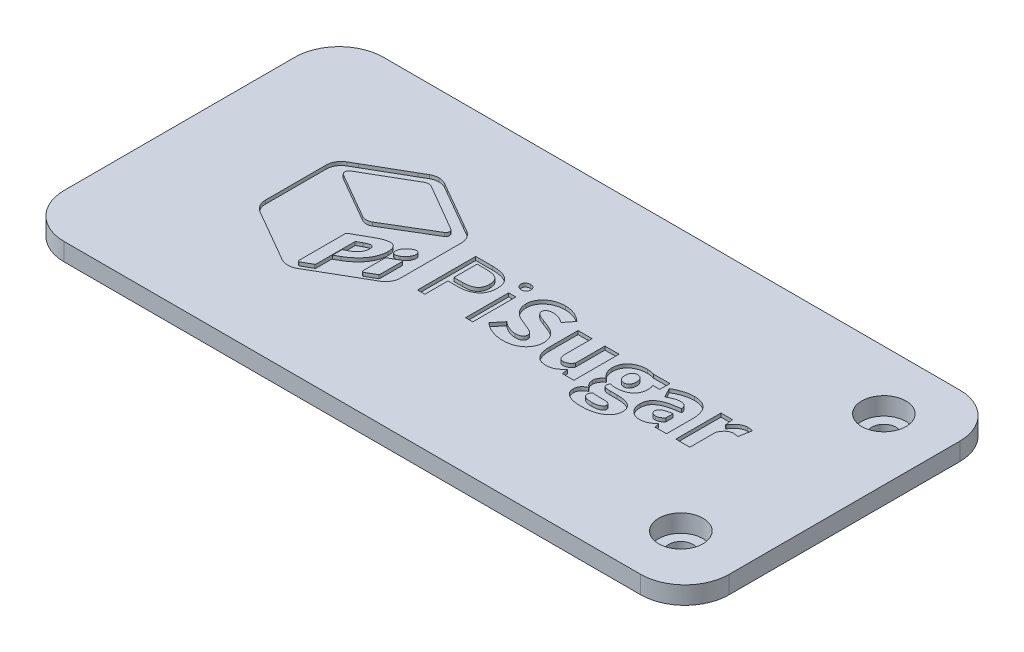
SolidWorks part; units mm, degrees
ref_plane "前视基准面" through (0, 0, 0) normal (0, 0, 1) x (1, 0, 0)
ref_plane "上视基准面" through (0, 0, 0) normal (0, 1, 0) x (1, 0, 0)
ref_plane "右视基准面" through (0, 0, 0) normal (1, 0, 0) x (0, 0, -1)
sketch "zero" plane through (0, 0, 0) normal (0, 1, 0) x (1, 0, 0)
  line L1 (-29.5, 15) -> (29.5, 15)
  line L2 (-32.5, 12) -> (-32.5, -12)
  line L3 (-29.5, -15) -> (29.5, -15)
  line L4 (32.5, 12) -> (32.5, -12)
  line L5 (-32.5, 15) -> (32.5, -15) construction
  line L6 (-32.5, -15) -> (32.5, 15) construction
  line L7 (-25.7, -15) -> (-14.5, -15)
  line L8 (-25.7, -15) -> (-25.7, -9.6569)
  line L9 (-25.7, -9.6569) -> (-14.5, -9.6569)
  line L10 (-14.5, -15) -> (-14.5, -9.6569)
  line L11 (5.2, -15) -> (12.7, -15)
  line L12 (5.2, -15) -> (5.2, -11)
  line L13 (5.2, -11) -> (12.7, -11)
  line L14 (12.7, -15) -> (12.7, -11)
  line L15 (17.8, -15) -> (25.3, -15)
  line L16 (17.8, -15) -> (17.8, -11)
  line L17 (17.8, -11) -> (25.3, -11)
  line L18 (25.3, -15) -> (25.3, -11)
  line L19 (-32.5, 7.7) -> (-19.5, 7.7)
  line L20 (-32.5, 7.7) -> (-32.5, -4.3)
  line L21 (-32.5, -4.3) -> (-19.5, -4.3)
  line L22 (-19.5, 7.7) -> (-19.5, -4.3)
  line L23 (-25.5, 14) -> (25.5, 14)
  line L24 (-25.5, 14) -> (-25.5, 8.8)
  line L25 (-25.5, 8.8) -> (25.5, 8.8)
  line L26 (25.5, 14) -> (25.5, 8.8)
  line L27 (-19.5, 7.2329) -> (-35.5, 7.2329)
  line L28 (-19.5, 7.2329) -> (-19.5, -3.7671)
  line L29 (-19.5, -3.7671) -> (-35.5, -3.7671)
  line L30 (-35.5, 7.2329) -> (-35.5, -3.7671)
  arc A0 (29.5, -15) -> (32.5, -12) centre (29.5, -12) ccw
  arc A1 (29.5, 15) -> (32.5, 12) centre (29.5, 12) cw
  arc A2 (-32.5, -12) -> (-29.5, -15) centre (-29.5, -12) ccw
  arc A3 (-29.5, 15) -> (-32.5, 12) centre (-29.5, 12) ccw
  circle A4 centre (-29, 11.4) radius 3
  circle A5 centre (-29, -11.5) radius 3
  circle A6 centre (29, 11.4) radius 3
  circle A7 centre (29, -11.5) radius 3
  circle A8 centre (-29, 11.4) radius 1.375
  circle A9 centre (-29, -11.5) radius 1.375
  circle A10 centre (29, -11.5) radius 1.375
  circle A11 centre (29, 11.4) radius 1.375
  point P0 (0, 0)
  dimension "D3" = 3
  dimension "D4" = 6
  dimension "D9" = 2.75
  dimension "D1" = 65
  dimension "D2" = 30
  dimension "D5" = 3.6
  dimension "D6" = 3.5
  dimension "D7" = 3.5
  dimension "D8" = 3.5
  dimension "D10" = 12
  dimension "D11" = 7.3
  dimension "D12" = 13
  dimension "D13" = 11.2
  dimension "D14" = 6.8
  dimension "D15" = 19.7
  dimension "D16" = 7.5
  dimension "D17" = 7.5
  dimension "D18" = 5.1
  dimension "D19" = 4
  dimension "D20" = 5.2
  dimension "D21" = 7
  dimension "D22" = 7
  dimension "D23" = 1
  dimension "D24" = 11
  dimension "D25" = 16
sketch "sugar" plane through (0, 0, 0) normal (0, 1, 0) x (1, 0, 0)
  line L1 (-29.5, 15) -> (29.5, 15)
  line L2 (-32.5, 12) -> (-32.5, -12)
  line L3 (-29.5, -15) -> (29.5, -15)
  line L4 (32.5, 12) -> (32.5, -12)
  line L5 (-32.5, 15) -> (32.5, -15) construction
  line L6 (-32.5, -15) -> (32.5, 15) construction
  line L7 (23.5, -11.5) -> (19.5, -11.5)
  line L8 (23.5, -11.5) -> (23.5, -13.9082)
  line L9 (23.5, -13.9082) -> (19.5, -13.9082)
  line L10 (19.5, -11.5) -> (19.5, -13.9082)
  line L11 (16, -11.0071) -> (8.5, -11.0071)
  line L12 (16, -11.0071) -> (16, -15)
  line L13 (16, -15) -> (8.5, -15)
  line L14 (8.5, -11.0071) -> (8.5, -15)
  line L15 (20.5, -13.9082) -> (22.5, -13.9082)
  line L16 (20.5, -13.9082) -> (20.5, -14.8173)
  line L17 (20.5, -14.8173) -> (22.5, -14.8173)
  line L18 (22.5, -13.9082) -> (22.5, -14.8173)
  arc A0 (29.5, 15) -> (32.5, 12) centre (29.5, 12) cw
  arc A1 (29.5, -15) -> (32.5, -12) centre (29.5, -12) ccw
  arc A2 (-32.5, -12) -> (-29.5, -15) centre (-29.5, -12) ccw
  arc A3 (-29.5, 15) -> (-32.5, 12) centre (-29.5, 12) ccw
  circle A4 centre (-29, 11.4) radius 3
  circle A5 centre (-29, 11.4) radius 1.375
  circle A6 centre (-29, -11.5) radius 3
  circle A7 centre (-29, -11.5) radius 1.375
  circle A8 centre (29, 11.4) radius 3
  circle A9 centre (29, 11.4) radius 1.375
  circle A10 centre (29, -11.5) radius 3
  circle A11 centre (29, -11.5) radius 1.375
  dimension "D3" = 3
  dimension "D1" = 65
  dimension "D2" = 30
  dimension "D4" = 9
  dimension "D5" = 4
  dimension "D6" = 3.5
  dimension "D7" = 7.5
  dimension "D8" = 2
  dimension "D9" = 1
sketch "case" plane through (0, 0, 0) normal (0, 1, 0) x (1, 0, 0)
  line L1 (-34.0422, 18) -> (30.9578, 18)
  line L2 (-39.0422, 13) -> (-39.0422, -13)
  line L3 (-34.0422, -18) -> (30.9578, -18)
  line L4 (35.9578, 13) -> (35.9578, -13)
  line L5 (-39.0422, 18) -> (35.9578, -18) construction
  line L6 (-39.0422, -18) -> (35.9578, 18) construction
  arc A0 (-39.0422, -13) -> (-34.0422, -18) centre (-34.0422, -13) ccw
  arc A1 (30.9578, -18) -> (35.9578, -13) centre (30.9578, -13) ccw
  arc A2 (30.9578, 18) -> (35.9578, 13) centre (30.9578, 13) cw
  arc A3 (-34.0422, 18) -> (-39.0422, 13) centre (-34.0422, 13) ccw
  point P0 (-1.5422, 0)
  point P3 (-1.5422, 0)
  dimension "D3" = 5
  dimension "D1" = 75
  dimension "D2" = 36
extrude "凸台-拉伸2" add sketch "case" along normal blind 2
sketch "草图2" plane through (0, 0, 0) normal (0, 1, 0) x (1, 0, 0)
  line L4 (-34.0422, -14.7) -> (30.9578, -14.7)
  line L5 (32.6578, -13) -> (32.6578, 13)
  line L6 (30.9578, 14.7) -> (-34.0422, 14.7)
  line L7 (-35.7422, 13) -> (-35.7422, -13)
  line L12 (33.8578, -13) -> (33.8578, 13)
  line L13 (30.9578, 15.9) -> (-34.0422, 15.9)
  line L14 (-36.9422, 13) -> (-36.9422, -13)
  line L15 (-34.0422, -15.9) -> (30.9578, -15.9)
  arc A4 (30.9578, -14.7) -> (32.6578, -13) centre (30.339, -12.3812) ccw
  arc A5 (32.6578, 13) -> (30.9578, 14.7) centre (30.339, 12.3812) ccw
  arc A6 (-34.0422, 14.7) -> (-35.7422, 13) centre (-33.4234, 12.3812) ccw
  arc A7 (-35.7422, -13) -> (-34.0422, -14.7) centre (-33.4234, -12.3812) ccw
  arc A12 (30.9578, -15.9) -> (33.8578, -13) centre (30.5796, -12.6217) ccw
  arc A13 (33.8578, 13) -> (30.9578, 15.9) centre (30.5796, 12.6217) ccw
  arc A14 (-34.0422, 15.9) -> (-36.9422, 13) centre (-33.6639, 12.6217) ccw
  arc A15 (-36.9422, -13) -> (-34.0422, -15.9) centre (-33.6639, -12.6217) ccw
  point P13 (0, 0)
extrude "凸台-拉伸3" add sketch "草图2" against normal blind 1
sketch "草图4" plane through (0, 0, 0) normal (0, 1, 0) x (1, 0, 0)
  line L1 (-35.7422, -5) -> (-31.7422, -5)
  line L2 (-35.7422, -5) -> (-35.7422, 5)
  line L3 (-35.7422, 5) -> (-31.7422, 5)
  line L4 (-31.7422, -5) -> (-31.7422, 5)
  line L5 (-35.7422, -5) -> (-31.7422, 5) construction
  line L6 (-35.7422, 5) -> (-31.7422, -5) construction
  line L7 (-35.7422, 13) -> (-35.7422, -13) construction
  point P0 (-33.7422, 0)
  dimension "D1" = 4
  dimension "D2" = 10
  dimension "D3" = 0
ref_plane "基准面1" through (33.8578, 0, 0) normal (1, 0, 0) x (0, 0, -1)
extrude "凸台-拉伸7" add sketch "草图4" against normal blind 2.2
ref_plane "基准面2" through (-36.9422, 0, 0) normal (-1, 0, 0) x (0, 0, 1)
ref_plane "基准面3" through (0, 2, 0) normal (0, 1, 0) x (1, 0, 0)
sketch "草图7" plane through (0, 2, 0) normal (0, 1, 0) x (1, 0, 0)
  line L0 (30.9578, 18) -> (-34.0422, 18) construction
  line L1 (-34.0422, -18) -> (30.9578, -18) construction
  line L2 (35.9578, -13) -> (35.9578, 13) construction
  circle A0 centre (28.9978, 11.4) radius 1.375
  circle A1 centre (28.9978, -11.5) radius 1.375
  dimension "D1" = 2.75
  dimension "D2" = 6.6
  dimension "D3" = 6.5
  dimension "D4" = 6.96
sketch "草图9" plane through (0, 2, 0) normal (0, 1, 0) x (1, 0, 0)
  circle A0 centre (28.9978, 11.4) radius 2.5
  circle A1 centre (28.9978, -11.5) radius 2.5
  dimension "D1" = 5
sketch "草图10" plane through (0, 2, 0) normal (0, 1, 0) x (1, 0, 0)
  circle A0 centre (28.9978, 11.4) radius 3.5
  circle A1 centre (28.9978, -11.5) radius 3.5
  dimension "D1" = 7
extrude "凸台-拉伸10" add sketch "草图10" against normal blind 3
extrude "切除-拉伸3" cut sketch "草图9" against normal blind 2
extrude "切除-拉伸4" cut sketch "草图7" against normal blind 4
ref_plane "基准面4" through (-31.7422, 0, 0) normal (1, 0, 0) x (0, 0, -1)
sketch "草图12" plane through (-31.7422, 0, 0) normal (1, 0, 0) x (0, 0, -1)
  line L1 (-5, -2.2) -> (5, -2.2)
  line L2 (-5, -2.2) -> (-5, -1)
  line L3 (-5, -1) -> (5, -1)
  line L4 (5, -2.2) -> (5, -1)
extrude "凸台-拉伸11" add sketch "草图12" against normal blind 6.7
chamfer "倒角5" distance 1 angle 45 1 edges at (-38.4422, -1, 0)
chamfer "倒角6" distance 1 angle 45 3 edges at (-33.7422, 0, -5) (-31.7422, 0, 0) (-33.7422, 0, 5)
chamfer "倒角8" distance 1 angle 45 1 edges at (-31.7422, -2.2, 0)
sketch "草图14" plane through (0, 2, 0) normal (0, 1, 0) x (1, 0, 0)
  line L0 (-12.3681, 5.7189) -> (-13.1887, 6.1919)
  line L1 (-13.1887, 6.1919) -> (-17.4456, 8.648)
  line L2 (-17.4456, 8.648) -> (-18.2661, 9.1267)
  line L3 (-19.9872, 9.1267) -> (-20.8078, 8.648)
  line L4 (-20.8078, 8.648) -> (-25.0647, 6.1919)
  line L5 (-25.0647, 6.1919) -> (-25.8853, 5.7189)
  line L6 (-26.7458, 4.2316) -> (-26.7458, -2.584)
  line L7 (-25.8853, -4.0714) -> (-25.0647, -4.5444)
  line L8 (-25.0647, -4.5444) -> (-20.8078, -7.0005)
  line L9 (-20.8078, -7.0005) -> (-19.9872, -7.4792)
  line L10 (-18.2661, -7.4792) -> (-17.4456, -7.0005)
  line L11 (-17.4456, -7.0005) -> (-13.1887, -4.5444)
  line L12 (-13.1887, -4.5444) -> (-12.3681, -4.0714)
  line L13 (-11.5076, -2.584) -> (-11.5076, 4.2316)
  line L14 (-24.7911, 5.0408) -> (-19.5256, 8.0839)
  line L15 (-18.7221, 8.0839) -> (-13.485, 5.0351)
  line L16 (-13.4793, 4.3341) -> (-18.5682, 1.2911)
  line L17 (-16.9897, -3.8662) -> (-17.5823, -4.1967)
  line L18 (-17.6394, -4.2936) -> (-17.6394, -6.0032)
  line L19 (-17.6963, -6.1001) -> (-18.8019, -6.7269)
  line L20 (-18.9671, -6.6301) -> (-18.9671, -1.3531)
  line L21 (-18.9102, -1.2562) -> (-17.0296, -0.1906)
  line L22 (-13.0862, -3.5129) -> (-14.1803, -4.134)
  line L23 (-14.3455, -4.0372) -> (-14.3455, -1.5241)
  line L24 (-14.2885, -1.4272) -> (-13.1944, -0.8117)
  line L25 (-13.0291, -0.9086) -> (-13.0291, -3.416)
  line L26 (-17.0581, -2.8519) -> (-17.5823, -3.114)
  line L27 (-17.6394, -2.9943) -> (-17.6394, -1.6494)
  line L28 (-17.5823, -1.5526) -> (-17.0923, -1.279)
  line L29 (-7.5129, 3.7529) -> (-9.3877, 3.7529)
  line L30 (-9.3877, 3.7529) -> (-9.3877, -2.812)
  line L31 (-9.3877, -2.812) -> (-8.5557, -2.812)
  line L32 (-8.5557, -2.812) -> (-8.5557, -0.2077)
  line L33 (-8.5557, -0.2077) -> (-7.4672, -0.2077)
  line L34 (-7.5755, 0.4648) -> (-8.5557, 0.4648)
  line L35 (-8.5557, 0.4648) -> (-8.5557, 3.0804)
  line L36 (-8.5557, 3.0804) -> (-7.6097, 3.0804)
  line L37 (-3.974, 2.0547) -> (-3.974, -2.812)
  line L38 (-3.974, -2.812) -> (-3.159, -2.812)
  line L39 (-3.159, -2.812) -> (-3.159, 2.0547)
  line L40 (-3.159, 2.0547) -> (-3.974, 2.0547)
  line L41 (1.548, 0.9776) -> (0.716, 1.3082)
  line L42 (1.8728, 2.0946) -> (2.6707, 3.0975)
  line L43 (-0.5605, 0.1342) -> (0.2886, -0.2248)
  line L44 (-1.2614, -0.8744) -> (-2.1674, -1.98)
  line L45 (6.6541, 2.2826) -> (6.6541, -1.0568)
  line L46 (5.2123, -0.6693) -> (5.2123, 2.2826)
  line L47 (5.2123, 2.2826) -> (3.6223, 2.2826)
  line L48 (3.6223, 2.2826) -> (3.6223, -0.8687)
  line L49 (6.8022, -2.111) -> (6.8364, -2.111)
  line L50 (6.8364, -2.111) -> (6.9504, -2.812)
  line L51 (6.9504, -2.812) -> (8.2496, -2.812)
  line L52 (8.2496, -2.812) -> (8.2496, 2.2826)
  line L53 (8.2496, 2.2826) -> (6.6541, 2.2826)
  line L54 (12.1019, -1.809) -> (11.2984, -1.809)
  line L55 (13.1961, 1.1315) -> (13.9825, 1.1315)
  line L56 (13.9825, 1.1315) -> (13.9825, 2.2826)
  line L57 (13.9825, 2.2826) -> (12.1134, 2.2826)
  line L58 (9.8623, -0.7605) -> (9.8623, -0.7946)
  line L59 (9.7655, -2.6239) -> (9.7655, -2.6695)
  line L60 (11.3155, -3.0285) -> (11.8, -3.0285)
  line L61 (14.4384, 1.7413) -> (14.9968, 0.6927)
  line L62 (17.2421, -2.2991) -> (17.282, -2.2991)
  line L63 (17.282, -2.2991) -> (17.3959, -2.812)
  line L64 (17.3959, -2.812) -> (18.6953, -2.812)
  line L65 (18.6953, -2.812) -> (18.6953, 0.0829)
  line L66 (17.0997, -0.4812) -> (17.0997, -1.2961)
  line L67 (21.1856, 1.3994) -> (21.1514, 1.3994)
  line L68 (21.1514, 1.3994) -> (21.0432, 2.2826)
  line L69 (21.0432, 2.2826) -> (19.7439, 2.2826)
  line L70 (19.7439, 2.2826) -> (19.7439, -2.812)
  line L71 (19.7439, -2.812) -> (21.3281, -2.812)
  line L72 (21.3281, -2.812) -> (21.3281, 0.1)
  line L73 (22.9864, 0.9321) -> (23.2542, 2.3054)
  line L74 (-17.5823, -3.114) -> (-17.5823, -4.1967)
  line L75 (-17.6394, -2.9943) -> (-17.6394, -4.2936)
  spline S0 degree 3 poles (-18.2661, 9.1267) (-18.534, 9.2749) (-18.8303, 9.3547) (-19.1266, 9.3547) knots 3 3 3 3 4 4 4 4
  spline S1 degree 3 poles (-19.1266, 9.3547) (-19.423, 9.3547) (-19.7193, 9.2749) (-19.9872, 9.1267) knots 4 4 4 4 5 5 5 5
  spline S2 degree 3 poles (-25.8853, 5.7189) (-26.4153, 5.4112) (-26.7458, 4.8413) (-26.7458, 4.2316) knots 8 8 8 8 9 9 9 9
  spline S3 degree 3 poles (-26.7458, -2.584) (-26.7458, -3.1995) (-26.4153, -3.7637) (-25.8853, -4.0714) knots 10 10 10 10 11 11 11 11
  spline S4 degree 3 poles (-19.9872, -7.4792) (-19.7193, -7.633) (-19.423, -7.7071) (-19.1266, -7.7071) knots 14 14 14 14 15 15 15 15
  spline S5 degree 3 poles (-19.1266, -7.7071) (-18.8303, -7.7071) (-18.534, -7.633) (-18.2661, -7.4792) knots 15 15 15 15 16 16 16 16
  spline S6 degree 3 poles (-12.3681, -4.0714) (-11.8324, -3.7637) (-11.5076, -3.1995) (-11.5076, -2.584) knots 19 19 19 19 20 20 20 20
  spline S7 degree 3 poles (-11.5076, 4.2316) (-11.5076, 4.8413) (-11.8324, 5.4112) (-12.3681, 5.7189) knots 21 21 21 21 22 22 22 22
  spline S8 degree 2 poles (-19.6795, 1.2911) (-24.831, 4.2658) (-24.8424, 4.2715) knots 0 0 0 1 1 1
  spline S9 degree 3 poles (-24.8424, 4.2715) (-25.1102, 4.4652) (-25.0818, 4.8755) (-24.7911, 5.0408) knots 1 1 1 1 2 2 2 2
  spline S10 degree 3 poles (-19.5256, 8.0839) (-19.2805, 8.2263) (-18.9728, 8.2263) (-18.7221, 8.0839) knots 3 3 3 3 4 4 4 4
  spline S11 degree 3 poles (-13.485, 5.0351) (-13.2172, 4.8812) (-13.2115, 4.4937) (-13.4793, 4.3341) knots 5 5 5 5 6 6 6 6
  spline S12 degree 3 poles (-18.5682, 1.2911) (-18.9102, 1.0916) (-19.3376, 1.0916) (-19.6795, 1.2911) knots 7 7 7 7 8 8 8 8
  spline S14 degree 3 poles (-17.6394, -6.0032) (-17.6394, -6.0431) (-17.6564, -6.0773) (-17.6963, -6.1001) knots 3 3 3 3 4 4 4 4
  spline S15 degree 3 poles (-18.8019, -6.7269) (-18.8759, -6.7668) (-18.9671, -6.7156) (-18.9671, -6.6301) knots 5 5 5 5 6 6 6 6
  spline S16 degree 3 poles (-18.9671, -1.3531) (-18.9671, -1.3132) (-18.95, -1.2733) (-18.9102, -1.2562) knots 7 7 7 7 8 8 8 8
  spline S17 degree 3 poles (-17.0296, -0.1906) (-15.8101, 0.499) (-14.8015, 0.6357) (-14.8015, -0.732) knots 9 9 9 9 10 10 10 10
  spline S18 degree 3 poles (-14.8015, -0.732) (-14.8015, -2.0484) (-15.8215, -3.2052) (-16.9897, -3.8662) knots 10 10 10 10 11 11 11 11
  spline S19 degree 3 poles (-13.0291, -3.416) (-13.0291, -3.4559) (-13.0519, -3.4958) (-13.0862, -3.5129) knots 0 0 0 0 1 1 1 1
  spline S20 degree 3 poles (-14.1803, -4.134) (-14.2543, -4.1739) (-14.3455, -4.1226) (-14.3455, -4.0372) knots 2 2 2 2 3 3 3 3
  spline S21 degree 3 poles (-14.3455, -1.5241) (-14.3455, -1.4842) (-14.3227, -1.45) (-14.2885, -1.4272) knots 4 4 4 4 5 5 5 5
  spline S22 degree 3 poles (-13.1944, -0.8117) (-13.1203, -0.7719) (-13.0291, -0.8231) (-13.0291, -0.9086) knots 6 6 6 6 7 7 7 7
  spline S23 degree 3 poles (-13.6845, 0.858) (-13.2457, 1.1087) (-12.9323, 1.0004) (-12.9323, 0.6015) (-12.9323, 0.2083) (-13.2457, -0.2533) (-13.6845, -0.4983) knots 2 2 2 2 3 3 3 4 4 4 4
  spline S24 degree 3 poles (-13.6845, -0.4983) (-14.1289, -0.7547) (-14.4424, -0.6465) (-14.4424, -0.2533) (-14.4424, 0.1514) (-14.1289, 0.6072) (-13.6845, 0.858) knots 0 0 0 0 1 1 1 2 2 2 2
  spline S25 degree 3 poles (-16.1007, -1.4671) (-16.1007, -2.0085) (-16.4084, -2.4871) (-17.0581, -2.8519) knots 0 0 0 0 1 1 1 1
  spline S27 degree 3 poles (-17.6394, -1.6494) (-17.6394, -1.6095) (-17.6166, -1.5697) (-17.5823, -1.5526) knots 4 4 4 4 5 5 5 5
  spline S28 degree 3 poles (-17.0923, -1.279) (-16.454, -0.9143) (-16.1007, -0.9086) (-16.1007, -1.4671) knots 6 6 6 6 7 7 7 7
  spline S29 degree 3 poles (-7.4672, -0.2077) (-6.0369, -0.2077) (-5.051, 0.442) (-5.051, 1.8268) knots 5 5 5 5 6 6 6 6
  spline S30 degree 3 poles (-5.051, 1.8268) (-5.051, 3.2628) (-6.0369, 3.7529) (-7.5129, 3.7529) knots 6 6 6 6 7 7 7 7
  spline S31 degree 3 poles (-7.6097, 3.0804) (-6.4585, 3.0804) (-5.8773, 2.7784) (-5.8773, 1.8268) knots 3 3 3 3 4 4 4 4
  spline S32 degree 3 poles (-5.8773, 1.8268) (-5.8773, 0.8865) (-6.4187, 0.4648) (-7.5755, 0.4648) knots 4 4 4 4 5 5 5 5
  spline S33 degree 3 poles (-3.5637, 3.0577) (-3.2389, 3.0577) (-2.9995, 3.2799) (-2.9995, 3.5819) (-2.9995, 3.9182) (-3.2389, 4.1119) (-3.5637, 4.1119) knots 2 2 2 2 3 3 3 4 4 4 4
  spline S34 degree 3 poles (-3.5637, 4.1119) (-3.8884, 4.1119) (-4.1278, 3.9182) (-4.1278, 3.5819) (-4.1278, 3.2799) (-3.8884, 3.0577) (-3.5637, 3.0577) knots 0 0 0 0 1 1 1 2 2 2 2
  spline S35 degree 3 poles (0.716, 1.3082) (0.1291, 1.5418) (-0.2926, 1.6843) (-0.2926, 2.0547) knots 1 1 1 1 2 2 2 2
  spline S36 degree 3 poles (-0.2926, 2.0547) (-0.2926, 2.408) (0.0094, 2.6075) (0.5052, 2.6075) knots 2 2 2 2 3 3 3 3
  spline S37 degree 3 poles (0.5052, 2.6075) (1.0237, 2.6075) (1.4341, 2.4308) (1.8728, 2.0946) knots 3 3 3 3 4 4 4 4
  spline S38 degree 3 poles (2.6707, 3.0975) (2.0894, 3.6845) (1.2745, 3.9808) (0.5052, 3.9808) knots 5 5 5 5 6 6 6 6
  spline S39 degree 3 poles (0.5052, 3.9808) (-0.9138, 3.9808) (-1.9167, 3.0804) (-1.9167, 1.9635) knots 6 6 6 6 7 7 7 7
  spline S40 degree 3 poles (-1.9167, 1.9635) (-1.9167, 0.9947) (-1.2614, 0.4135) (-0.5605, 0.1342) knots 7 7 7 7 8 8 8 8
  spline S41 degree 3 poles (0.2886, -0.2248) (0.8585, -0.4641) (1.2289, -0.5895) (1.2289, -0.977) knots 9 9 9 9 10 10 10 10
  spline S42 degree 3 poles (1.2289, -0.977) (1.2289, -1.336) (0.9497, -1.5582) (0.357, -1.5582) knots 10 10 10 10 11 11 11 11
  spline S43 degree 3 poles (0.357, -1.5582) (-0.1672, -1.5582) (-0.7884, -1.279) (-1.2614, -0.8744) knots 11 11 11 11 12 12 12 12
  spline S44 degree 3 poles (-2.1674, -1.98) (-1.4779, -2.6125) (-0.5434, -2.9373) (0.3228, -2.9373) knots 13 13 13 13 14 14 14 14
  spline S45 degree 3 poles (0.3228, -2.9373) (1.9356, -2.9373) (2.8701, -1.9629) (2.8701, -0.8516) knots 14 14 14 14 15 15 15 15
  spline S46 degree 3 poles (2.8701, -0.8516) (2.8701, 0.0886) (2.3744, 0.6471) (1.548, 0.9776) knots 15 15 15 15 16 16 16 16
  spline S47 degree 3 poles (6.6541, -1.0568) (6.3862, -1.4329) (6.1639, -1.5754) (5.805, -1.5754) knots 1 1 1 1 2 2 2 2
  spline S48 degree 3 poles (5.805, -1.5754) (5.4003, -1.5754) (5.2123, -1.3759) (5.2123, -0.6693) knots 2 2 2 2 3 3 3 3
  spline S49 degree 3 poles (3.6223, -0.8687) (3.6223, -2.1395) (4.0954, -2.9373) (5.2066, -2.9373) knots 6 6 6 6 7 7 7 7
  spline S50 degree 3 poles (5.2066, -2.9373) (5.9018, -2.9373) (6.3805, -2.6125) (6.8022, -2.111) knots 7 7 7 7 8 8 8 8
  spline S51 degree 3 poles (11.2984, -1.809) (10.7514, -1.809) (10.5462, -1.7007) (10.5462, -1.4671) knots 1 1 1 1 2 2 2 2
  spline S52 degree 3 poles (10.5462, -1.4671) (10.5462, -1.2961) (10.5861, -1.2163) (10.7057, -1.1081) knots 2 2 2 2 3 3 3 3
  spline S53 degree 3 poles (10.7057, -1.1081) (10.9281, -1.1707) (11.1331, -1.1993) (11.3041, -1.1993) knots 3 3 3 3 4 4 4 4
  spline S54 degree 3 poles (11.3041, -1.1993) (12.4324, -1.1993) (13.3386, -0.6807) (13.3386, 0.5103) knots 4 4 4 4 5 5 5 5
  spline S55 degree 3 poles (13.3386, 0.5103) (13.3386, 0.7554) (13.2758, 0.989) (13.1961, 1.1315) knots 5 5 5 5 6 6 6 6
  spline S56 degree 3 poles (12.1134, 2.2826) (11.8797, 2.3681) (11.6005, 2.408) (11.3041, 2.408) knots 9 9 9 9 10 10 10 10
  spline S57 degree 3 poles (11.3041, 2.408) (10.2043, 2.408) (9.1728, 1.8039) (9.1728, 0.5559) knots 10 10 10 10 11 11 11 11
  spline S58 degree 3 poles (9.1728, 0.5559) (9.1728, -0.0367) (9.5034, -0.5097) (9.8623, -0.7605) knots 11 11 11 11 12 12 12 12
  spline S59 degree 3 poles (9.8623, -0.7946) (9.5318, -1.0283) (9.2982, -1.3873) (9.2982, -1.7463) knots 13 13 13 13 14 14 14 14
  spline S60 degree 3 poles (9.2982, -1.7463) (9.2982, -2.1737) (9.4977, -2.4416) (9.7655, -2.6239) knots 14 14 14 14 15 15 15 15
  spline S61 degree 3 poles (9.7655, -2.6695) (9.2925, -2.9089) (9.0418, -3.2508) (9.0418, -3.6725) knots 16 16 16 16 17 17 17 17
  spline S62 degree 3 poles (9.0418, -3.6725) (9.0418, -4.5842) (10.0048, -4.9547) (11.1788, -4.9547) knots 17 17 17 17 18 18 18 18
  spline S63 degree 3 poles (11.1788, -4.9547) (12.951, -4.9547) (14.0623, -4.1911) (14.0623, -3.114) knots 18 18 18 18 19 19 19 19
  spline S64 degree 3 poles (14.0623, -3.114) (14.0623, -2.1908) (13.3557, -1.809) (12.1019, -1.809) knots 19 19 19 19 20 20 20 20
  spline S65 degree 3 poles (11.3041, -0.2419) (10.9395, -0.2419) (10.6602, 0.026) (10.6602, 0.5559) (10.6602, 1.0745) (10.9395, 1.3424) (11.3041, 1.3424) knots 2 2 2 2 3 3 3 4 4 4 4
  spline S66 degree 3 poles (11.3041, 1.3424) (11.6802, 1.3424) (11.9481, 1.0745) (11.9481, 0.5559) (11.9481, 0.026) (11.6802, -0.2419) (11.3041, -0.2419) knots 0 0 0 0 1 1 1 2 2 2 2
  spline S67 degree 3 poles (11.4295, -3.9574) (10.7742, -3.9574) (10.3468, -3.7807) (10.3468, -3.4217) knots 0 0 0 0 1 1 1 1
  spline S68 degree 3 poles (10.3468, -3.4217) (10.3468, -3.2508) (10.4265, -3.1083) (10.5861, -2.9658) knots 1 1 1 1 2 2 2 2
  spline S69 degree 3 poles (10.5861, -2.9658) (10.7514, -3.0114) (10.9452, -3.0285) (11.3155, -3.0285) knots 2 2 2 2 3 3 3 3
  spline S70 degree 3 poles (11.8, -3.0285) (12.2729, -3.0285) (12.5408, -3.0912) (12.5408, -3.3932) knots 4 4 4 4 5 5 5 5
  spline S71 degree 3 poles (12.5408, -3.3932) (12.5408, -3.7181) (12.0849, -3.9574) (11.4295, -3.9574) knots 5 5 5 5 6 6 6 6
  spline S72 degree 3 poles (16.6324, 2.408) (15.8402, 2.408) (15.1109, 2.1402) (14.4384, 1.7413) knots 0 0 0 0 1 1 1 1
  spline S73 degree 3 poles (14.9968, 0.6927) (15.5041, 0.9776) (15.9258, 1.1372) (16.3304, 1.1372) knots 2 2 2 2 3 3 3 3
  spline S74 degree 3 poles (16.3304, 1.1372) (16.8489, 1.1372) (17.0655, 0.8979) (17.0997, 0.4876) knots 3 3 3 3 4 4 4 4
  spline S75 degree 3 poles (17.0997, 0.4876) (15.1109, 0.271) (14.2674, -0.3102) (14.2674, -1.3873) knots 4 4 4 4 5 5 5 5
  spline S76 degree 3 poles (14.2674, -1.3873) (14.2674, -2.2364) (14.843, -2.9373) (15.7833, -2.9373) knots 5 5 5 5 6 6 6 6
  spline S77 degree 3 poles (15.7833, -2.9373) (16.3475, -2.9373) (16.8204, -2.6752) (17.2421, -2.2991) knots 6 6 6 6 7 7 7 7
  spline S78 degree 3 poles (18.6953, 0.0829) (18.6953, 1.6786) (17.9488, 2.408) (16.6324, 2.408) knots 11 11 11 11 12 12 12 12
  spline S79 degree 3 poles (17.0997, -1.2961) (16.866, -1.5469) (16.6552, -1.7007) (16.3304, -1.7007) knots 0 0 0 0 1 1 1 1
  spline S80 degree 3 poles (16.3304, -1.7007) (15.9998, -1.7007) (15.7833, -1.5582) (15.7833, -1.2619) knots 1 1 1 1 2 2 2 2
  spline S81 degree 3 poles (15.7833, -1.2619) (15.7833, -0.9029) (16.1081, -0.618) (17.0997, -0.4812) knots 2 2 2 2 3 3 3 3
  spline S82 degree 3 poles (22.6388, 2.408) (22.1259, 2.408) (21.5617, 2.0775) (21.1856, 1.3994) knots 0 0 0 0 1 1 1 1
  spline S83 degree 3 poles (21.3281, 0.1) (21.5959, 0.7725) (22.0518, 1.0118) (22.4279, 1.0118) knots 7 7 7 7 8 8 8 8
  spline S84 degree 3 poles (22.4279, 1.0118) (22.6559, 1.0118) (22.804, 0.9776) (22.9864, 0.9321) knots 8 8 8 8 9 9 9 9
  spline S85 degree 3 poles (23.2542, 2.3054) (23.1117, 2.3681) (22.9408, 2.408) (22.6388, 2.408) knots 10 10 10 10 11 11 11 11
extrude "切除-拉伸8" cut sketch "草图14" against normal blind 0.4
